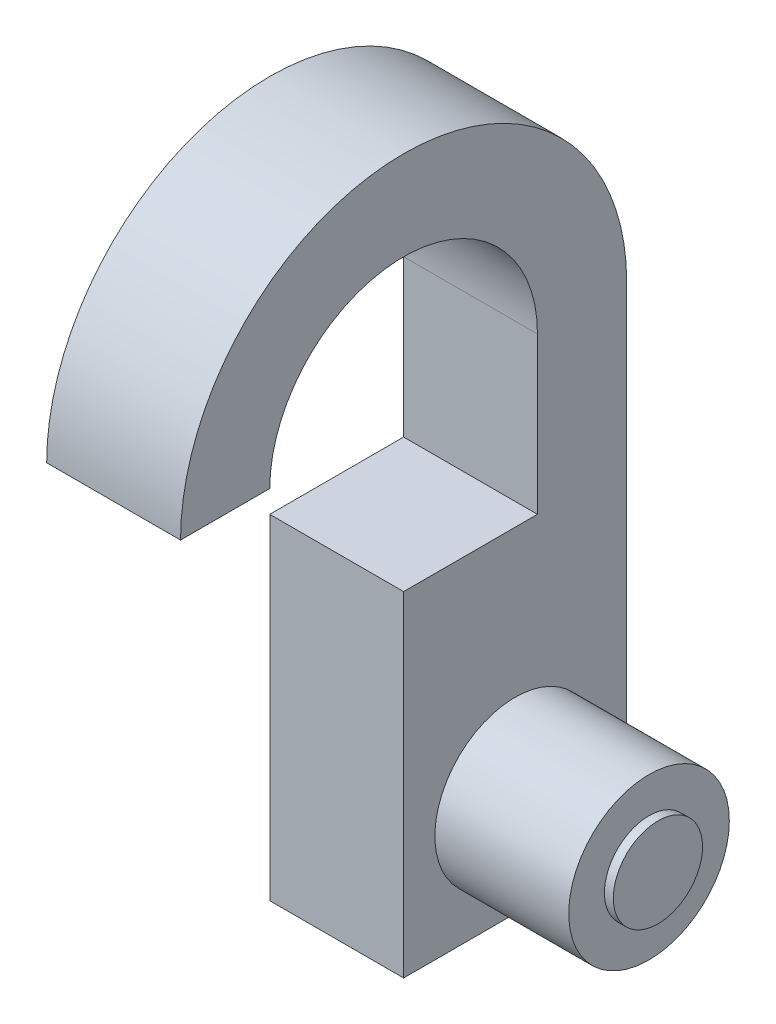
SolidWorks part; units mm, degrees
ref_plane "Plano frontal" through (0, 0, 0) normal (0, 0, 1) x (1, 0, 0)
ref_plane "Plano superior" through (0, 0, 0) normal (0, 1, 0) x (1, 0, 0)
ref_plane "Plano direito" through (0, 0, 0) normal (1, 0, 0) x (0, 0, -1)
sketch "Esboço1" plane through (0, 0, 0) normal (1, 0, 0) x (0, 0, -1)
  line L0 (-250, -375) -> (250, -375)
  line L1 (-250, -375) -> (-250, 375)
  line L2 (250, -375) -> (250, 375)
  line L3 (-250, 375) -> (250, 375)
  line L4 (-250, -375) -> (250, 375) construction
  line L5 (250, -375) -> (-250, 375) construction
  line L6 (250, -375) -> (0, -375) construction
  line L7 (0, -375) -> (0, -135) construction
  line L8 (250, 375) -> (50, 375) construction
  line L9 (50, 375) -> (250, 375)
  line L10 (50, 375) -> (50, 725)
  line L11 (250, 375) -> (250, 725)
  line L12 (50, 725) -> (250, 725)
  circle A0 centre (0, -135) radius 180
  circle A1 centre (0, -135) radius 100
  point P1 (0, 0)
  dimension "D4" = 360
  dimension "D5" = 200
  dimension "D1" = 750
  dimension "D2" = 500
  dimension "D3" = 240
  dimension "D6" = 200
  dimension "D7" = 350
extrude "Ressalto-extrusão2" add sketch "Esboço1" along normal blind 620 contours A1 region at (0, -135, 0)
extrude "Ressalto-extrusão6" add sketch "Esboço1<9>" along normal blind 600 contours A0 A1 region at (0, -135, 174.9088)
sketch "Esboço1<9>" plane through (0, 0, 0) normal (1, 0, 0) x (0, 0, -1) same geometry as "Esboço1"
extrude "Ressalto-extrusão7" add sketch "Esboço1<10>" along normal blind 300 contours L3 L1 L0 L2 A0 region at (0, 50.2954, 0)
sketch "Esboço1<10>" plane through (0, 0, 0) normal (1, 0, 0) x (0, 0, -1) same geometry as "Esboço1"
sketch "Esboço3" plane through (0, 375, 0) normal (0, 1, 0) x (1, 0, 0)
  line L0 (0, 250) -> (0, 50) construction
  line L1 (0, -250) -> (0, 250) construction
  line L3 (0, 50) -> (300, 50)
  line L4 (0, 50) -> (0, 250)
  line L5 (0, 250) -> (300, 250)
  line L6 (300, 50) -> (300, 250)
  dimension "D1" = 200
extrude "Ressalto-extrusão8" add sketch "Esboço3" along normal blind 350
sketch "Esboço5" plane through (300, 0, 0) normal (1, 0, 0) x (0, 0, -1)
  line L0 (50, 725) -> (-250, 725) construction
  line L1 (-750, 725) -> (-550, 725)
  line L2 (250, 725) -> (50, 725)
  arc A0 (50, 725) -> (-550, 725) centre (-250, 725) ccw
  arc A1 (250, 725) -> (-750, 725) centre (-250, 725) ccw
  dimension "D1" = 300
sketch "Esboço6" plane through (0, 0, 0) normal (-1, 0, 0) x (0, 0, 1)
  line L0 (-50, 725) -> (250, 725) construction
  line L1 (-250, 725) -> (-50, 725) construction
  line L2 (-50, 725) -> (-50, 375) construction
  dimension "D1" = 300
extrude "Ressalto-extrusão9" add sketch "Esboço5" against normal blind 300 contours A1 L1 A0 L2
